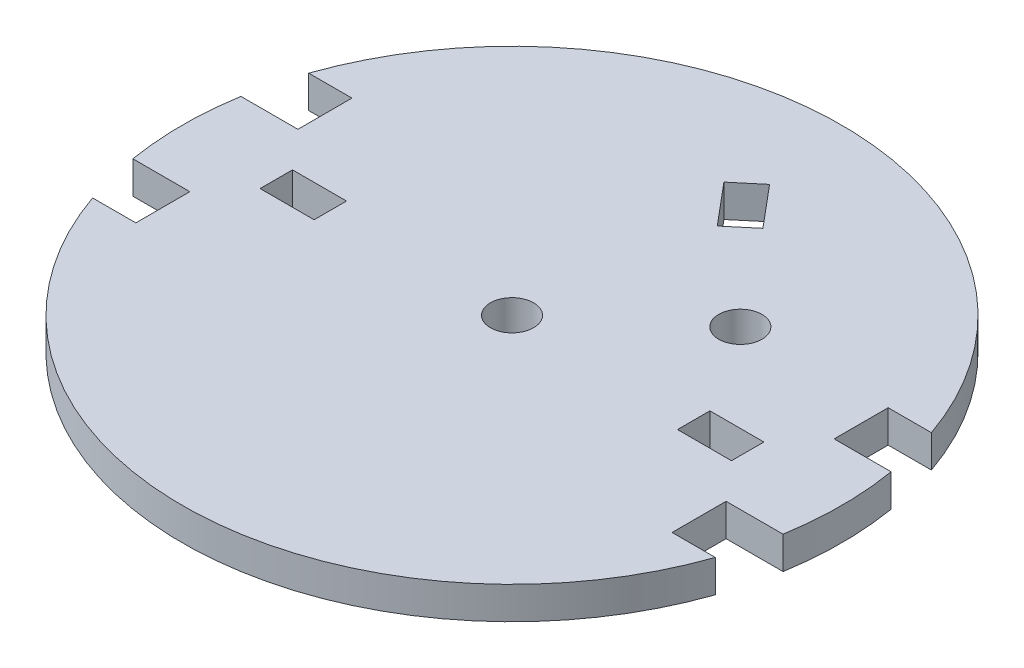
SolidWorks part; units mm, degrees
ref_plane "Alzado" through (0, 0, 0) normal (0, 0, 1) x (1, 0, 0)
ref_plane "Planta" through (0, 0, 0) normal (0, 1, 0) x (1, 0, 0)
ref_plane "Vista lateral" through (0, 0, 0) normal (1, 0, 0) x (0, 0, -1)
sketch "Croquis1" plane through (0, 0, 0) normal (0, 1, 0) x (1, 0, 0)
  circle A0 centre (0, 0) radius 30.5
extrude "Saliente-Extruir1" add sketch "Croquis1" along normal blind 3
sketch "Croquis2" plane through (0, 3, 0) normal (0, 1, 0) x (1, 0, 0)
  circle A0 centre (0, 0) radius 2
extrude "Cortar-Extruir1" cut sketch "Croquis2" against normal blind 4
sketch "Croquis5" plane through (0, 3, 0) normal (0, 1, 0) x (1, 0, 0)
  line L0 (0, 0) -> (0, 10)
  line L1 (28.8141, -5) -> (30.0874, -5)
  line L2 (28.8141, 5) -> (30.0874, 5)
  line L3 (-24.8141, 10) -> (-28.8141, 10)
  line L4 (24.8141, -5) -> (24.8141, -10)
  line L5 (-24.8141, -10) -> (-28.8141, -10)
  line L6 (24.8141, -5) -> (28.8141, -5)
  line L7 (24.8141, 5) -> (24.8141, 10)
  line L8 (-24.8141, 5) -> (-28.8141, 5)
  line L9 (-24.8141, 5) -> (-24.8141, 10)
  line L10 (-24.8141, -5) -> (-28.8141, -5)
  line L11 (-24.8141, -5) -> (-24.8141, -10)
  line L12 (24.8141, 5) -> (28.8141, 5)
  line L13 (24.8141, -10) -> (28.8141, -10)
  line L14 (24.8141, 10) -> (28.8141, 10)
  line L15 (-28.8141, 5) -> (-30.0874, 5)
  line L16 (-28.8141, -5) -> (-30.0874, -5)
  circle A1 centre (0, 0) radius 30.5 construction
  arc A2 (-28.8141, 10) -> (-30.0874, 5) centre (0, 0) ccw
  arc A3 (28.8141, 10) -> (28.8141, -10) centre (0, 0) cw
  arc A4 (-30.0874, -5) -> (-28.8141, -10) centre (0, 0) ccw
  arc A5 (30.0874, -5) -> (28.8141, -10) centre (0, 0) cw
  arc A6 (28.8141, 10) -> (30.0874, 5) centre (0, 0) cw
  circle M2 centre (0, 0) radius 30.5
extrude "Cortar-Extruir3" cut sketch "Croquis5" against normal blind 4 contours L11 L10 L8 L9 L3 L5 M2 | L15 L8 L9 L3 M2 | L14 L7 L12 L2 M2 | L4 L13 L1 L6 M2 region at (27.1844, 3, 7.3876) region at (27.1844, 3, -7.3876) region at (-27.1844, 3, 7.3876) region at (-27.1844, 3, -7.3876)
sketch "Croquis6" plane through (0, 3, 0) normal (0, 1, 0) x (1, 0, 0)
  line L1 (-16.8141, -1.5) -> (-16.8141, 1.5)
  line L2 (-16.8141, 1.5) -> (-21.8141, 1.5)
  line L3 (-21.8141, 1.5) -> (-21.8141, -1.5)
  line L4 (-16.8141, -1.5) -> (-21.8141, -1.5)
  line L5 (16.8141, -1.5) -> (21.8141, -1.5)
  line L6 (21.8141, 1.5) -> (21.8141, -1.5)
  line L7 (16.8141, 1.5) -> (21.8141, 1.5)
  line L8 (16.8141, -1.5) -> (16.8141, 1.5)
extrude "Cortar-Extruir4" cut sketch "Croquis6" against normal blind 4
sketch "Croquis7" plane through (0, 3, 0) normal (0, 1, 0) x (1, 0, 0)
  line L0 (-8.1011, 29.1011) -> (9.5756, 8.0348)
  line L1 (9.5756, 8.0348) -> (27.2522, -13.0314)
  line L2 (-8.1011, 29.1011) -> (-27.2522, 13.0314)
  line L3 (27.2522, -13.0314) -> (8.1011, -29.1011)
  line L4 (8.1011, -29.1011) -> (-27.2522, 13.0314)
  line L5 (1.4284, 22.4114) -> (-0.8697, 20.4831)
  line L6 (1.4284, 22.4114) -> (4.6423, 18.5812)
  line L7 (4.6423, 18.5812) -> (2.3442, 16.6528)
  line L8 (2.3442, 16.6528) -> (-0.8697, 20.4831)
  circle A0 centre (11.4907, 9.6418) radius 2
  point P7 (-9.5756, -8.0348)
extrude "Cortar-Extruir5" cut sketch "Croquis7" against normal blind 4 contours A0 | L7 L6 L5 L0 region at (1.8863, 3, -19.5321) region at (11.4907, 3, -9.6418)
